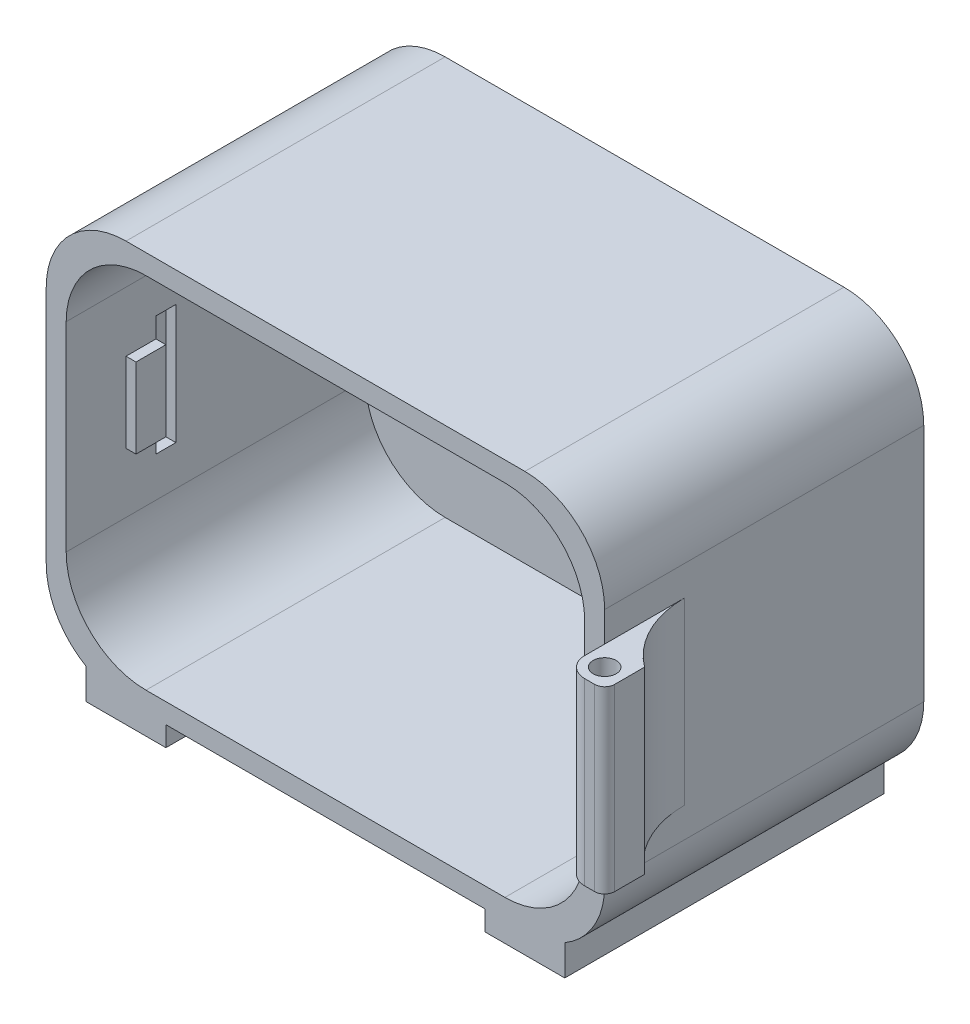
SolidWorks part; units mm, degrees
ref_plane "Front Plane" through (0, 0, 0) normal (0, 0, 1) x (1, 0, 0)
ref_plane "Top Plane" through (0, 0, 0) normal (0, 1, 0) x (1, 0, 0)
ref_plane "Right Plane" through (0, 0, 0) normal (1, 0, 0) x (0, 0, -1)
sketch "Sketch1" plane through (0, 0, 0) normal (0, 0, 1) x (1, 0, 0)
  line L0 (-82.55, 31.75) -> (-82.55, -31.75)
  line L1 (-63.5, 63.5) -> (63.5, 63.5)
  line L2 (-88.9, 38.1) -> (-88.9, -38.1)
  line L3 (-63.5, -63.5) -> (63.5, -63.5)
  line L4 (88.9, 38.1) -> (88.9, -38.1)
  line L5 (-88.9, 63.5) -> (88.9, -63.5) construction
  line L6 (-88.9, -63.5) -> (88.9, 63.5) construction
  line L7 (-57.15, -57.15) -> (57.15, -57.15)
  line L8 (82.55, 31.75) -> (82.55, -31.75)
  line L9 (-57.15, 57.15) -> (57.15, 57.15)
  line L10 (-88.9, 63.5) -> (88.9, 63.5) construction
  line L11 (88.9, 63.5) -> (88.9, -63.5) construction
  line L12 (82.55, 57.15) -> (82.55, -57.15) construction
  line L13 (-82.55, 57.15) -> (82.55, 57.15) construction
  line L14 (-82.55, -57.15) -> (82.55, -57.15) construction
  line L15 (-88.9, -63.5) -> (88.9, -63.5) construction
  line L16 (-82.55, 57.15) -> (-82.55, -57.15) construction
  line L17 (-88.9, 63.5) -> (-88.9, -63.5) construction
  arc A0 (63.5, 63.5) -> (88.9, 38.1) centre (63.5, 38.1) cw
  arc A1 (82.55, 31.75) -> (57.15, 57.15) centre (57.15, 31.75) ccw
  arc A2 (57.15, -57.15) -> (82.55, -31.75) centre (57.15, -31.75) ccw
  arc A3 (63.5, -63.5) -> (88.9, -38.1) centre (63.5, -38.1) ccw
  arc A4 (-82.55, -31.75) -> (-57.15, -57.15) centre (-57.15, -31.75) ccw
  arc A5 (-88.9, -38.1) -> (-63.5, -63.5) centre (-63.5, -38.1) ccw
  arc A6 (-63.5, 63.5) -> (-88.9, 38.1) centre (-63.5, 38.1) ccw
  arc A7 (-82.55, 31.75) -> (-57.15, 57.15) centre (-57.15, 31.75) cw
  point P0 (0, 0)
  dimension "D4" = 25.4
  dimension "D1" = 177.8
  dimension "D2" = 127
  dimension "D3" = 6.35
extrude "Boss-Extrude1" add sketch "Sketch1" against normal blind 95.25
sketch "Sketch2" plane through (0, 0, -95.25) normal (0, 0, -1) x (-1, 0, 0)
  line L0 (-63.5, 63.5) -> (63.5, 63.5)
  line L1 (-63.5, 63.5) -> (63.5, 63.5) construction
  line L2 (0, 63.5) -> (0, -63.5) construction
  line L3 (63.5, -63.5) -> (-63.5, -63.5) construction
  line L4 (63.5, -63.5) -> (-63.5, -63.5)
  line L5 (-88.9, -38.1) -> (-88.9, 38.1) construction
  line L6 (-88.9, -38.1) -> (-88.9, 38.1)
  line L7 (88.9, -38.1) -> (88.9, 38.1)
  arc A0 (-88.9, 38.1) -> (-63.5, 63.5) centre (-63.5, 38.1) cw
  arc A1 (-63.5, -63.5) -> (-88.9, -38.1) centre (-63.5, -38.1) cw
  arc A2 (-88.9, -38.1) -> (-63.5, -63.5) centre (-63.5, -38.1) ccw construction
  arc A3 (63.5, -63.5) -> (88.9, -38.1) centre (63.5, -38.1) ccw
  arc A4 (88.9, 38.1) -> (63.5, 63.5) centre (63.5, 38.1) ccw
extrude "Boss-Extrude2" add sketch "Sketch2" along normal blind 6.35
sketch "Sketch4" plane through (0, -63.5, 0) normal (0, -1, 0) x (1, 0, 0)
  line L0 (-76.2, 0) -> (-50.8, 0)
  line L2 (-76.2, 0) -> (-76.2, -101.6)
  line L3 (-88.9, -101.6) -> (-63.5, -101.6) construction
  line L4 (-76.2, -101.6) -> (-50.8, -101.6)
  line L5 (63.5, -101.6) -> (-63.5, -101.6) construction
  line L6 (-50.8, -101.6) -> (-50.8, 0)
  line L7 (0, 0) -> (0, -101.6) construction
  line L8 (-63.5, 0) -> (63.5, 0) construction
  line L9 (76.2, -101.6) -> (50.8, -101.6)
  line L10 (76.2, 0) -> (76.2, -101.6)
  line L11 (76.2, 0) -> (50.8, 0)
  line L12 (50.8, -101.6) -> (50.8, 0)
  point P4 (-63.5, 0)
  dimension "D1" = 25.4
extrude "Boss-Extrude3" add sketch "Sketch4" along normal blind 6.35 and the other way up to next
sketch "Sketch5" plane through (0, 0, 0) normal (0, 1, 0) x (1, 0, 0)
  line L0 (0, 0) -> (88.9, 0) construction
  line L1 (63.5, 0) -> (-63.5, 0) construction
  line L2 (95.25, 0) -> (101.6, 0) construction
  line L3 (88.9, 25.4) -> (88.9, 0)
  line L4 (95.25, 0) -> (95.25, -6.35) construction
  line L7 (101.6, -12.7) -> (88.9, -12.7)
  line L8 (101.6, -12.7) -> (101.6, 0)
  line L9 (101.6, 0) -> (95.25, 0)
  line L10 (88.9, -12.7) -> (88.9, 0)
  line L11 (101.6, -12.7) -> (88.9, 0) construction
  line L12 (101.6, 0) -> (88.9, -12.7) construction
  line L13 (88.9, -6.35) -> (101.6, -6.35) construction
  arc A3 (101.6, 0) -> (88.9, 25.4) centre (120.65, 25.4) cw
  circle A4 centre (95.25, -6.35) radius 3.675
  point P4 (98.425, 0)
  dimension "D2" = 7.35
  dimension "D1" = 6.35
  dimension "D3" = 88.9
  dimension "D4" = 25.4
extrude "Boss-Extrude5" add sketch "Sketch5" along normal blind 28.575 and the other way blind 28.575 contours A3 L3 L10 L7 L8 A4 region at (94.0273, 0, 0.7656)
fillet "Fillet1" radius 3.175 1 edges at (101.6, 0, 12.7)
sketch "Sketch6" plane through (0, 28.575, 0) normal (0, 1, 0) x (1, 0, 0)
  line L0 (91.575, -6.35) -> (88.9, -6.35) construction
  line L1 (88.9, 0) -> (88.9, -12.7) construction
  line L2 (97.1007, -9.525) -> (101.6, -9.525) construction
  circle A0 centre (95.25, -6.35) radius 3.675 construction
sketch "Sketch8" plane through (-82.55, 0, 0) normal (1, 0, 0) x (0, 0, -1)
  line L0 (0, -19.05) -> (28.575, -19.05) construction
  line L1 (0, 31.75) -> (0, -31.75) construction
  line L2 (28.575, -19.05) -> (34.925, -19.05)
  line L3 (34.925, -19.05) -> (34.925, 19.05)
  line L4 (34.925, 19.05) -> (28.575, 19.05)
  line L5 (28.575, 19.05) -> (28.575, -19.05)
  line L6 (95.25, -57.15) -> (0, -57.15) construction
  dimension "D1" = 28.575
  dimension "D2" = 6.35
  dimension "D3" = 38.1
  dimension "D4" = 38.1
extrude "Cut-Extrude1" cut sketch "Sketch8" against normal blind 3.175
sketch "Sketch10" plane through (-82.55, 0, 0) normal (1, 0, 0) x (0, 0, -1)
  line L0 (28.575, 0) -> (28.575, 12.7) construction
  line L1 (28.575, 19.05) -> (28.575, -19.05) construction
  line L3 (28.575, 12.7) -> (19.05, 12.7)
  line L4 (28.575, 12.7) -> (28.575, -12.7)
  line L5 (28.575, -12.7) -> (19.05, -12.7)
  line L6 (19.05, 12.7) -> (19.05, -12.7)
  point P7 (28.575, 0)
  dimension "D1" = 12.7
  dimension "D2" = 9.525
extrude "Boss-Extrude6" add sketch "Sketch10" along normal blind 3.175
sketch "Sketch11" plane through (0, 0, -101.6) normal (0, 0, -1) x (-1, 0, 0)
  line L0 (32.462, -188.0741) -> (352.462, -188.0741) construction
  line L1 (-8.558, 38.2776) -> (9.4147, 38.2776)
  line L2 (9.4147, 38.2776) -> (12.3761, 30.5166)
  line L3 (12.3761, 30.5166) -> (6.5554, 30.5166)
  line L4 (-8.558, 38.2776) -> (-26.541, -14.1457)
  line L5 (-26.541, -14.1457) -> (-20.9531, -14.1457)
  line L6 (-20.9531, -17.5278) -> (-27.8644, -17.5278)
  line L7 (-27.8644, -17.5278) -> (-30.0702, -24.7333)
  line L8 (-30.0702, -24.7333) -> (-9.6303, -24.7333)
  line L9 (-9.6303, -24.7333) -> (-7.4245, -17.5278)
  line L10 (-7.4245, -17.5278) -> (8.4569, -17.5278)
  line L11 (8.4569, -17.5278) -> (10.5156, -24.7333)
  line L12 (10.5156, -24.7333) -> (12.3761, -24.7333)
  line L13 (12.3761, -24.7333) -> (12.3761, -18.8513)
  line L14 (16.1034, -18.8513) -> (16.1034, -24.7333)
  line L15 (16.1034, -24.7333) -> (21.2502, -24.7333)
  line L16 (21.2502, -24.7333) -> (21.2502, -18.8513)
  line L17 (24.3382, -18.8513) -> (24.3382, -24.7333)
  line L18 (24.3382, -24.7333) -> (31.2496, -24.7333)
  line L19 (31.2496, -24.7333) -> (13.3095, 27.1753)
  line L20 (13.3095, 27.1753) -> (6.5554, 27.1753)
  line L21 (0.7548, 15.0295) -> (-4.8523, -6.6891)
  line L22 (-4.8523, -6.6891) -> (6.0184, -6.6891)
  line L23 (6.0184, -6.6891) -> (0.7548, 15.0295)
  arc A0 (6.5554, 30.5166) -> (6.5554, 27.1753) centre (2.9252, 28.8459) ccw
  arc A1 (12.3761, -18.8513) -> (16.1034, -18.8513) centre (14.2398, -15.2135) cw
  arc A2 (-20.9531, -14.1457) -> (-20.9531, -17.5278) centre (-17.0513, -15.8368) cw
  arc A3 (21.2502, -18.8513) -> (24.3382, -18.8513) centre (22.7942, -15.1977) cw
  circle A4 centre (2.9252, 28.8459) radius 1.6706
  circle A5 centre (-17.0513, -15.8368) radius 2.045
  circle A6 centre (14.2398, -15.2135) radius 2.3144
  circle A7 centre (22.7942, -15.1977) radius 1.5563
  circle A8 centre (0, 3.175) radius 44.8241
  dimension "D1" = 3.175
extrude "Cut-Extrude4" cut sketch "Sketch11" against normal blind 1.5875 contours A8 | L22 L23 L21 | A3 L17 L18 L19 L20 A0 L3 L2 L1 L4 L5 A2 L6 L7 L8 L9 L10 L11 L12 L13 A1 L14 L15 L16
sketch "Sketch12" plane through (0, 0, -101.6) normal (0, 0, -1) x (-1, 0, 0)
  line L0 (0, 0) -> (0, -57.15) construction
  line L1 (63.5, -57.15) -> (-63.5, -57.15) construction
  text T0 "amp-lab.org" font "Century Gothic" height in points 48
  point P6 (0, -57.15)
  dimension "D1" = 57.15
  dimension "D2" = 127
extrude "Cut-Extrude5" cut sketch "Sketch12" against normal blind 1.5875
fillet "Fillet2" radius 6.35 1 edges at (88.9, 0, 12.7)
